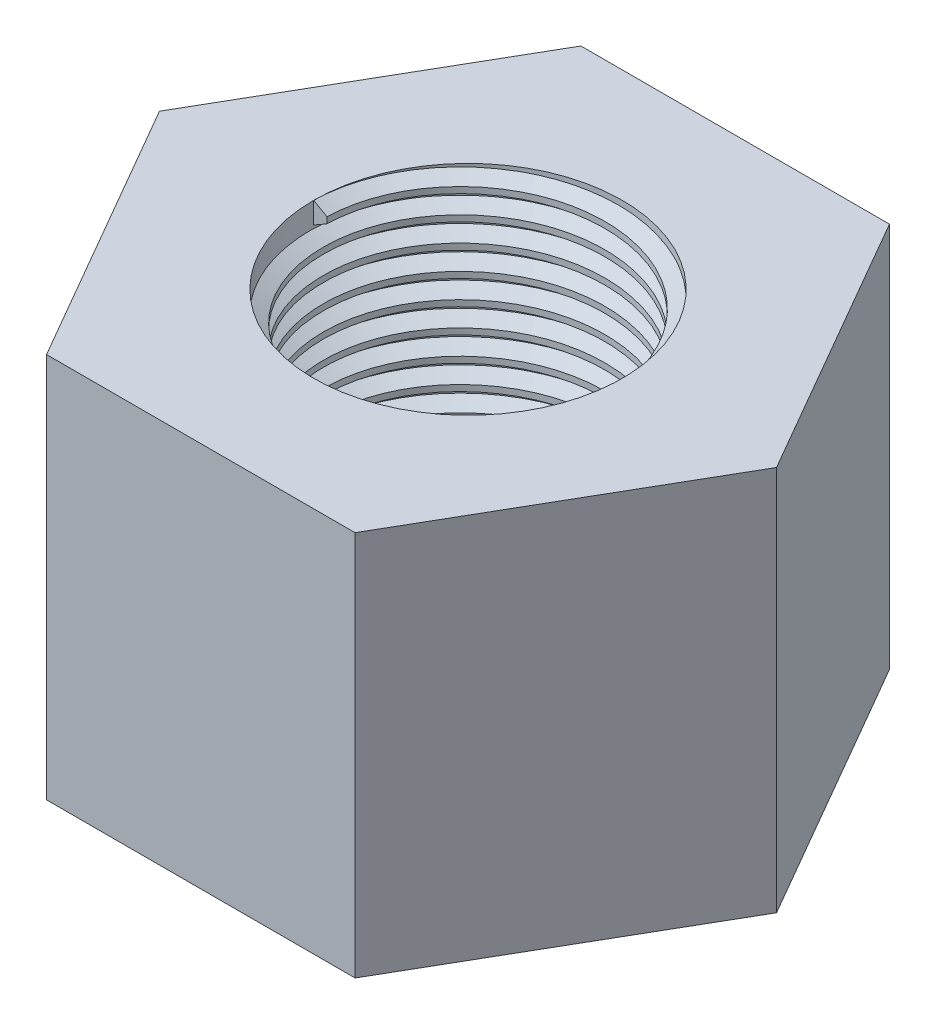
SolidWorks part; units mm, degrees
material "A286 Iron Base Superalloy"
ref_plane "Front Plane" through (0, 0, 0) normal (0, 0, 1) x (1, 0, 0)
ref_plane "Top Plane" through (0, 0, 0) normal (0, 1, 0) x (1, 0, 0)
ref_plane "Right Plane" through (0, 0, 0) normal (1, 0, 0) x (0, 0, -1)
sketch "Sketch1" plane through (0, 0, 0) normal (0, 1, 0) x (1, 0, 0)
  line L1 (2, 3.4641) -> (-2, 3.4641)
  line L2 (-2, 3.4641) -> (-4, 0)
  line L3 (-4, 0) -> (-2, -3.4641)
  line L4 (-2, -3.4641) -> (2, -3.4641)
  line L5 (2, -3.4641) -> (4, 0)
  line L6 (4, 0) -> (2, 3.4641)
  circle A0 centre (0, 0) radius 3.4641 construction
  circle A1 centre (0, 0) radius 2
  dimension "D1" = 4
  dimension "D2" = 4
extrude "Boss-Extrude1" add sketch "Sketch1" along normal blind 5
thread "Thread1" pitch 0.3175 method extrude profile "Thread Profile3" start angle 0, offset 0, length 5, pitch 0.3175, diameter 4
ref_plane "Plane3" through (-2, 5, 0) normal (0, 0, 1) x (-1, 0, 0)
sketch "Thread Profile3" plane through (-2, 5, 0) normal (0, 0, 1) x (-1, 0, 0)
  line L0 (0, 0) -> (0, 0.3175) construction
  line L11 (0, 0) -> (0, 0.2778)
  line L12 (0, 0.2778) -> (-0.1719, 0.1786)
  line L13 (-0.1719, 0.1786) -> (-0.1719, 0.0992)
  line L15 (-0.1719, 0.0992) -> (0, 0)
  line L17 (-0.1719, 0.1389) -> (0, 0.1389) construction
  point P2 (0, 0)
  dimension "Pitch" = 0.3175
  dimension "Profile_Angle" = 60
  dimension "Profile_Land" = 0.0794
  dimension "Profile_Height" = 0.1719
sketch "Sketch8" plane through (0, 0, -3.4641) normal (0, 0, -1) x (-1, 0, 0)
  line L1 (-4, 0) -> (4, 0)
  line L2 (-4, 0) -> (-4, -2)
  line L3 (-4, -2) -> (4, -2)
  line L4 (4, 0) -> (4, -2)
  dimension "D1" = 8
  dimension "D2" = 2
extrude "Cut-Extrude1" cut sketch "Sketch8" against normal through all
